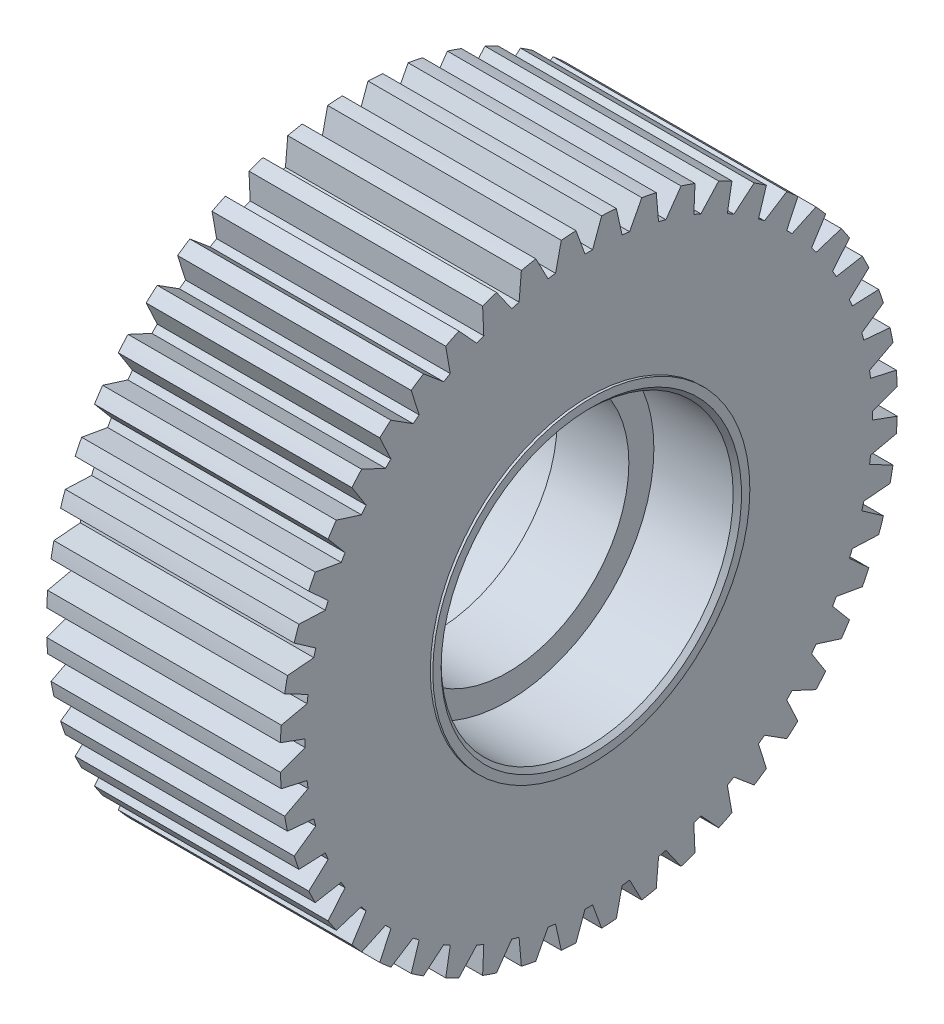
SolidWorks part; units mm, degrees
material "1.7131 (16MnCr5)"
ref_plane "Vorne" through (0, 0, 0) normal (0, 0, 1) x (1, 0, 0)
ref_plane "Oben" through (0, 0, 0) normal (0, 1, 0) x (1, 0, 0)
ref_plane "Rechts" through (0, 0, 0) normal (1, 0, 0) x (0, 0, -1)
ref_axis "Achse1" through (-15.73, 0, 0) along (1, 0, 0)
sketch "Skizze1" plane through (0, 0, 0) normal (0, 0, 1) x (1, 0, 0)
  line L0 (-36.0104, 0) -> (46.5768, 0) construction
  line L1 (-14.3, 19) -> (-14.3, 18)
  line L2 (-13.8, 17.5) -> (-4.3, 17.5)
  line L3 (-4.3, 17.5) -> (-4.3, 14.5)
  line L4 (-4.3, 14.5) -> (4.3, 14.5)
  line L5 (4.3, 14.5) -> (4.3, 17.5)
  line L6 (4.3, 17.5) -> (13.8, 17.5)
  line L7 (14.3, 18) -> (14.3, 19)
  line L8 (14.3, 19) -> (14, 19)
  line L9 (14, 19) -> (14, 37)
  line L10 (14, 37) -> (-14, 37)
  line L11 (-14, 37) -> (-14, 19)
  line L12 (-14, 19) -> (-14.3, 19)
  line L13 (0, 0) -> (0, 20) construction
  line L16 (-14.3, 18) -> (-13.8, 17.5)
  line L17 (13.8, 17.5) -> (14.3, 18)
  point P4 (-14.3, 17.5)
  point P5 (14.3, 17.5)
  point P8 (0, 14.5)
  dimension "D1" = 35
  dimension "D2" = 10
  dimension "D3" = 29
  dimension "D4" = 28.6
  dimension "D5" = 74
  dimension "D6" = 38
  dimension "D7" = 28
revolve "Rotation1" add sketch "Skizze1" angle 360 about L0
sketch "Skizze2" plane through (14, 0, 0) normal (1, 0, 0) x (0, 0, -1)
  line L0 (0, 0) -> (0, 74.3665) construction
  line L1 (0.456, 33.9969) -> (1.5374, 36.968)
  line L2 (-0.456, 33.9969) -> (-1.5374, 36.968)
  circle A0 centre (0, 0) radius 34 construction
  circle A1 centre (0, 0) radius 36 construction
  circle A2 centre (0, 0) radius 37 construction
  arc A3 (0.456, 33.9969) -> (-0.456, 33.9969) centre (0, 0) ccw
  arc A4 (1.5374, 36.968) -> (-1.5374, 36.968) centre (0, 0) ccw
  point P10 (1.178, 35.9807)
  point P11 (-1.178, 35.9807)
  dimension "D1" = 68
  dimension "D2" = 72
  dimension "D3" = 74
  dimension "D4" = 20
  dimension "D5" = 2.356
extrude "Schnitt-Linear austragen1" cut sketch "Skizze2" against normal up to next
pattern_circular "Kreismuster1" count 48 over 360 about axis through (-15.73, 0, 0) along (1, 0, 0) of "Schnitt-Linear austragen1"
sketch "Skizze3" plane through (14.3, 0, 0) normal (1, 0, 0) x (0, 0, -1)
  circle A0 centre (0, 0) radius 36 construction
  dimension "D1" = 72
